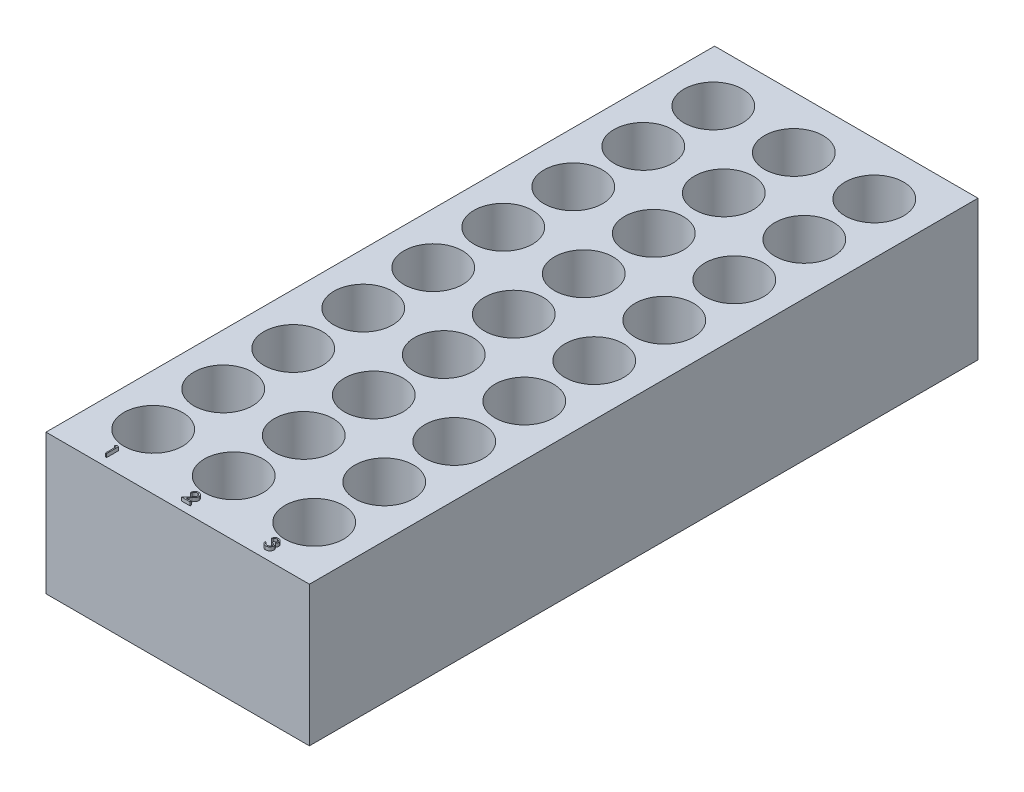
SolidWorks part; units mm, degrees
ref_plane "Front Plane" through (0, 0, 0) normal (0, 0, 1) x (1, 0, 0)
ref_plane "Top Plane" through (0, 0, 0) normal (0, 1, 0) x (1, 0, 0)
ref_plane "Right Plane" through (0, 0, 0) normal (1, 0, 0) x (0, 0, -1)
sketch "Sketch1" plane through (0, 0, 0) normal (0, 1, 0) x (1, 0, 0)
  line L0 (-23, 60.5) -> (-37.625, 60.5) construction
  line L1 (37.625, -95.5) -> (-37.625, -95.5)
  line L2 (37.625, -95.5) -> (37.625, 95.5)
  line L3 (37.625, 95.5) -> (-37.625, 95.5)
  line L4 (-37.625, -95.5) -> (-37.625, 95.5)
  line L5 (37.625, -95.5) -> (-37.625, 95.5) construction
  line L6 (37.625, 95.5) -> (-37.625, -95.5) construction
  line L7 (-23, 80.5) -> (-37.625, 80.5) construction
  line L8 (-23, 80.5) -> (-23, 95.5) construction
  line L9 (23, 80.5) -> (37.625, 80.5) construction
  line L10 (-8.375, 80.5) -> (-23, 80.5) construction
  circle A0 centre (-23, 80.5) radius 8.375
  circle A1 centre (0, 80.5) radius 8.375
  circle A2 centre (23, 80.5) radius 8.375
  circle A6 centre (-23, 60.5) radius 8.375
  circle A7 centre (0, 60.5) radius 8.375
  circle A8 centre (23, 60.5) radius 8.375
  circle A12 centre (-23, 40.5) radius 8.375
  circle A13 centre (0, 40.5) radius 8.375
  circle A14 centre (23, 40.5) radius 8.375
  circle A18 centre (-23, 20.5) radius 8.375
  circle A19 centre (0, 20.5) radius 8.375
  circle A20 centre (23, 20.5) radius 8.375
  circle A24 centre (-23, 0.5) radius 8.375
  circle A25 centre (0, 0.5) radius 8.375
  circle A26 centre (23, 0.5) radius 8.375
  circle A30 centre (-23, -19.5) radius 8.375
  circle A31 centre (0, -19.5) radius 8.375
  circle A32 centre (23, -19.5) radius 8.375
  circle A36 centre (-23, -39.5) radius 8.375
  circle A37 centre (0, -39.5) radius 8.375
  circle A38 centre (23, -39.5) radius 8.375
  circle A42 centre (-23, -59.5) radius 8.375
  circle A43 centre (0, -59.5) radius 8.375
  circle A44 centre (23, -59.5) radius 8.375
  circle A48 centre (-23, -79.5) radius 8.375
  circle A49 centre (0, -79.5) radius 8.375
  circle A50 centre (23, -79.5) radius 8.375
  point P0 (0, 0)
  dimension "D1" = 16.75
  dimension "D3" = 20
  dimension "D5" = 15
  dimension "D7" = 191
  dimension "D9" = 75.25
  dimension "D2" = 3
  dimension "D6" = 9
extrude "Boss-Extrude1" add sketch "Sketch1" along normal blind 30
sketch "Sketch2" plane through (0, 0, 0) normal (0, -1, 0) x (1, 0, 0)
  line L1 (37.625, -95.5) -> (-37.625, -95.5)
  line L2 (37.625, -95.5) -> (37.625, 95.5)
  line L3 (37.625, 95.5) -> (-37.625, 95.5)
  line L4 (-37.625, -95.5) -> (-37.625, 95.5)
  line L5 (37.625, -95.5) -> (-37.625, 95.5) construction
  line L6 (37.625, 95.5) -> (-37.625, -95.5) construction
  point P0 (0, 0)
sketch "Sketch3" plane through (0, 0, 0) normal (0, -1, 0) x (1, 0, 0)
  line L1 (-37.625, 95.5) -> (37.625, 95.5)
  line L2 (-37.625, 95.5) -> (-37.625, -95.5)
  line L3 (-37.625, -95.5) -> (37.625, -95.5)
  line L4 (37.625, 95.5) -> (37.625, -95.5)
extrude "Boss-Extrude2" add sketch "Sketch3" along normal blind 10
sketch "Sketch4" plane through (0, 30, 0) normal (0, 1, 0) x (1, 0, 0)
  text T0 "1               2               3"
extrude "Boss-Extrude3" add sketch "Sketch4" along normal blind 1
